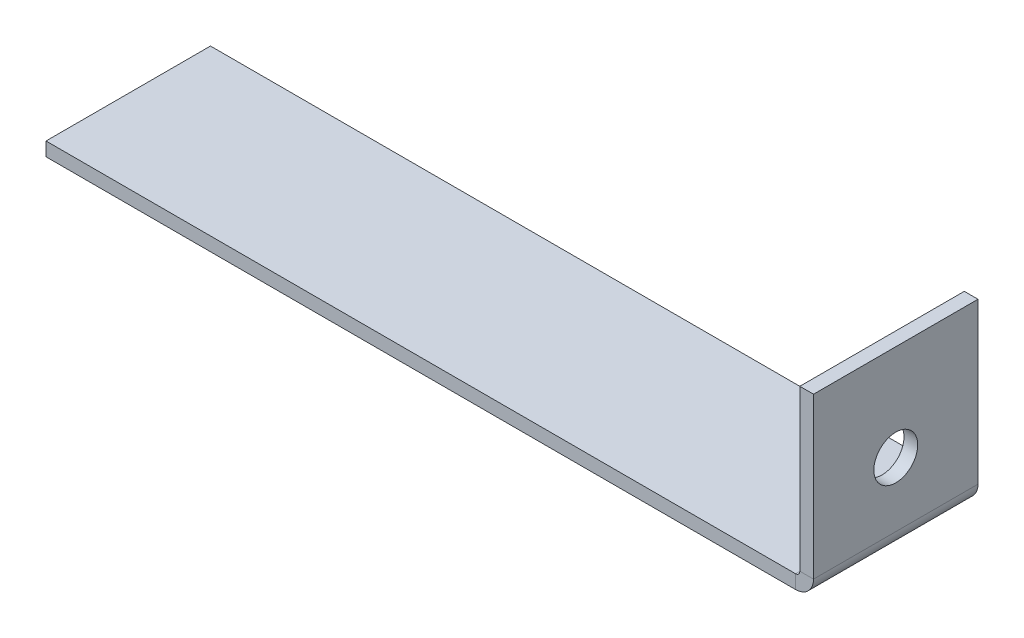
SolidWorks part; units mm, degrees
note: The reader was unsure of these and kept them because the rebuilt part matched: flange length of "Edge-Flange1".
ref_plane "Front Plane" through (0, 0, 0) normal (0, 0, 1) x (1, 0, 0)
ref_plane "Top Plane" through (0, 0, 0) normal (0, 1, 0) x (1, 0, 0)
ref_plane "Right Plane" through (0, 0, 0) normal (1, 0, 0) x (0, 0, -1)
sketch "Sketch2" plane through (0, 0, 0) normal (0, 1, 0) x (1, 0, 0)
  line L1 (0, 0) -> (177.8, 0)
  line L2 (0, 0) -> (0, 38.1)
  line L3 (0, 38.1) -> (177.8, 38.1)
  line L4 (177.8, 0) -> (177.8, 38.1)
  dimension "D1" = 177.8
  dimension "2in" = 38.1
base flange "Base-Flange1" sketch "Sketch2" thickness 3.175 reverse thickness direction no parameters "D1"=1
edge flange "Edge-Flange1" sketch "Sketch9" flange angle 90 flange length 41.275 flange position material inside bend radius 1 thickness 3.175 relief rectangular parameters "D6"=10
sketch "Sketch9" plane through (177.8, 0, 0) normal (1, 0, 0) x (0, 0, -1)
  line L2 (0, 0) -> (0, 38.1)
  line L3 (0, 38.1) -> (38.1, 38.1)
  line L4 (38.1, 38.1) -> (38.1, 0)
  line L7 (0, 0) -> (38.1, 0) construction
  line L8 (0, 0) -> (38.1, 0)
  dimension "D1" = 38.1
bend "EdgeBend1" bend radius 1 bend angle 90 parameters "D5"=1
sketch "Sketch10" plane through (174.625, 0, 0) normal (-1, 0, 0) x (0, 0, 1)
  line L1 (-38.1, 38.1) -> (0, 38.1) construction
  line L3 (-307.2973, -9.525) -> (213.4027, -9.525) construction
  circle A0 centre (-19.05, 15.875) radius 5.08
  point P6 (-19.05, 38.1)
  dimension "D1" = 10.16
  dimension "D2" = 25.4
extrude "Cut-Extrude1" cut sketch "Sketch10" against normal up to next normal cut yes
sketch "Bend-Lines1" [suppressed] plane through (0, 0, 0) normal (0, 1, 0) x (1, 0, 0)
sketch "Bounding-Box1" [suppressed] plane through (0, 0, 0) normal (0, 1, 0) x (1, 0, 0)
sheet metal parameters "Sheet-Metal1" thickness 3.175 parameters "D1"=1
flat pattern "Flat-Pattern1" [suppressed]
sketch "Bend-Lines2" plane through (0, 0, 0) normal (0, 1, 0) x (1, 0, 0)
sketch3d "Bounding-Box2" [suppressed]
  line L0 (-133.9121, 39.4719, 0) -> (0, 39.4719, 0) construction
  line L1 (-133.9121, 0, 0) -> (0, 0, 0) construction
  line L2 (-133.9121, 39.4719, 0) -> (-133.9121, 0, 0) construction
  line L3 (0, 39.4719, 0) -> (0, 0, 0) construction
sheet metal parameters "Sheet-Metal2" thickness 3.175 parameters "D1"=1
flat pattern "Flat-Pattern1"
sketch "Bend-Lines2" plane through (0, 0, 0) normal (0, 1, 0) x (1, 0, 0)
  line L0 (162.9572, 0) -> (162.9572, 25.4) construction
  line L1 (162.9572, 0) -> (162.9572, 25.4) construction
sketch3d "Bounding-Box2" [suppressed]
  line L0 (224.3144, 25.4, 0) -> (0, 25.4, 0) construction
  line L1 (224.3144, 0, 0) -> (0, 0, 0) construction
  line L2 (224.3144, 25.4, 0) -> (224.3144, 0, 0) construction
  line L3 (0, 25.4, 0) -> (0, 0, 0) construction
bend of the flat pattern "Flatten-<EdgeBend1>1"
sheet metal parameters "Sheet-Metal3" thickness 3.175 parameters "D1"=1
flat pattern "Flat-Pattern1"
sketch "Bend-Lines2" plane through (0, 0, 0) normal (0, 1, 0) x (1, 0, 0)
  line L0 (175.6572, 0) -> (175.6572, 38.1) construction
  line L1 (175.6572, 0) -> (175.6572, 38.1) construction
sketch3d "Bounding-Box2" [suppressed]
  line L0 (214.7894, 38.1, 0) -> (0, 38.1, 0) construction
  line L1 (214.7894, 0, 0) -> (0, 0, 0) construction
  line L2 (214.7894, 38.1, 0) -> (214.7894, 0, 0) construction
  line L3 (0, 38.1, 0) -> (0, 0, 0) construction
bend of the flat pattern "Flatten-<EdgeBend1>1" [suppressed]
